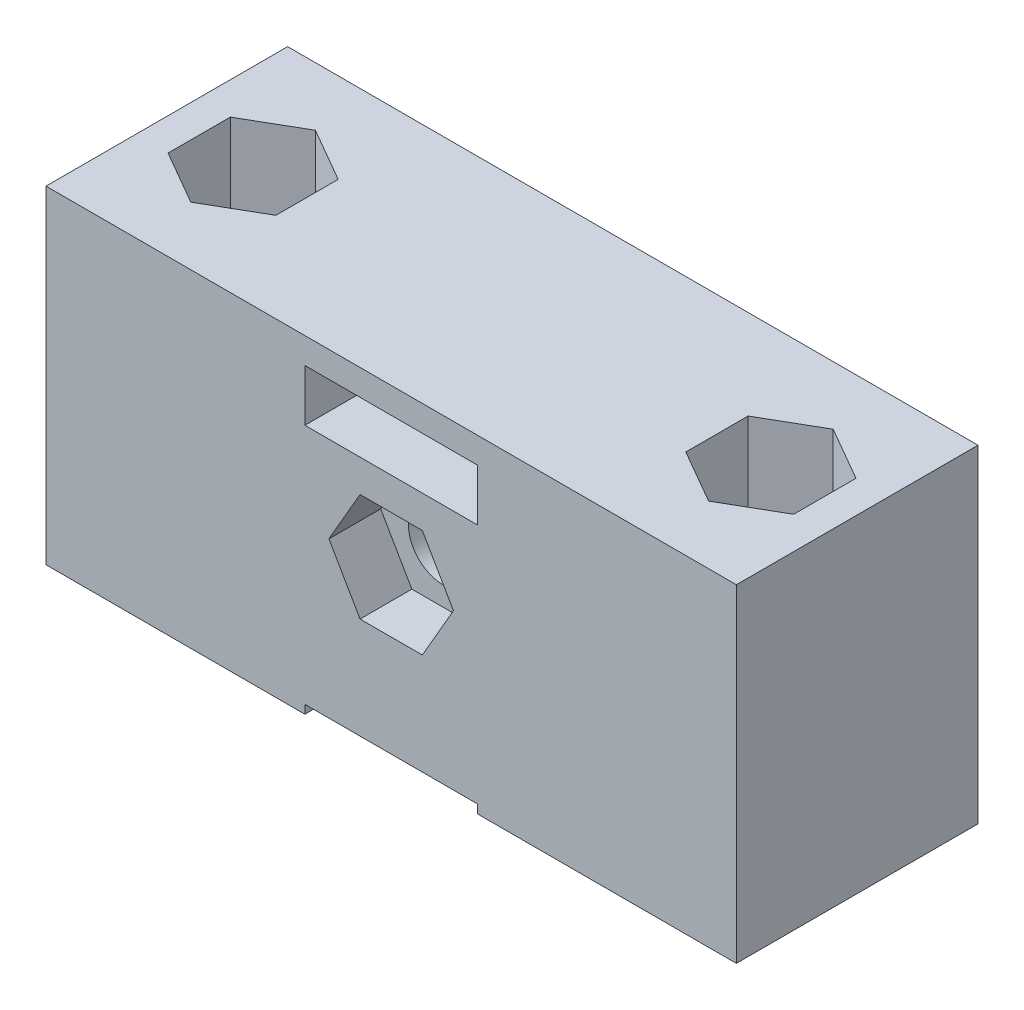
SolidWorks part; units mm, degrees
ref_plane "Front Plane" through (0, 0, 0) normal (0, 0, 1) x (1, 0, 0)
ref_plane "Top Plane" through (0, 0, 0) normal (0, 1, 0) x (1, 0, 0)
ref_plane "Right Plane" through (0, 0, 0) normal (1, 0, 0) x (0, 0, -1)
sketch "Sketch1" plane through (0, 0, 0) normal (0, 1, 0) x (1, 0, 0)
  line L1 (-20, 7) -> (20, 7)
  line L2 (-20, 7) -> (-20, -7)
  line L3 (-20, -7) -> (20, -7)
  line L4 (20, 7) -> (20, -7)
  line L5 (-20, 7) -> (20, -7) construction
  line L6 (-20, -7) -> (20, 7) construction
  point P0 (0, 0)
  dimension "D1" = 40
  dimension "D2" = 14
extrude "Boss-Extrude1" add sketch "Sketch1" along normal blind 19
sketch "Sketch2" plane through (0, 0, 7) normal (0, 0, 1) x (1, 0, 0)
  line L0 (0, 19) -> (0, 0) construction
  line L1 (-20, 19) -> (20, 19) construction
  line L3 (-5, 14.5) -> (5, 14.5)
  line L4 (-5, 14.5) -> (-5, 17.5)
  line L5 (-5, 17.5) -> (5, 17.5)
  line L6 (5, 14.5) -> (5, 17.5)
  line L7 (-5, 14.5) -> (5, 17.5) construction
  line L8 (-5, 17.5) -> (5, 14.5) construction
  line L9 (-5, -0.5) -> (5, -0.5)
  line L10 (-5, -0.5) -> (-5, 0.5)
  line L11 (-5, 0.5) -> (5, 0.5)
  line L12 (5, -0.5) -> (5, 0.5)
  line L13 (-5, -0.5) -> (5, 0.5) construction
  line L14 (-5, 0.5) -> (5, -0.5) construction
  point P5 (0, 16)
  dimension "D1" = 10
  dimension "D2" = 3
  dimension "D3" = 16
  dimension "D4" = 10
  dimension "D5" = 1
extrude "Cut-Extrude1" cut sketch "Sketch2" against normal blind 30
sketch "Sketch3" plane through (0, 0, 7) normal (0, 0, 1) x (1, 0, 0)
  line L0 (0, 19) -> (0, 0) construction
  line L1 (-20, 19) -> (20, 19) construction
  circle A0 centre (0, 9.5) radius 2
  dimension "D1" = 4
extrude "Cut-Extrude2" cut sketch "Sketch3" against normal through all
sketch "Sketch4" plane through (0, 19, 0) normal (0, 1, 0) x (1, 0, 0)
  line L0 (-20, 0) -> (20, 0) construction
  line L1 (-20, 7) -> (-20, -7) construction
  line L2 (20, -7) -> (20, 7) construction
  line L3 (0, 7) -> (0, -7) construction
  line L4 (20, 7) -> (-20, 7) construction
  line L5 (-20, -7) -> (20, -7) construction
  circle A0 centre (-15, 0) radius 1.6
  circle A1 centre (15, 0) radius 1.6
  dimension "D1" = 3.2
  dimension "D2" = 15
extrude "Cut-Extrude3" cut sketch "Sketch4" against normal through all
sketch "Sketch8" plane through (0, 0, 0) normal (0, -1, 0) x (-1, 0, 0)
  line L0 (-5, 7) -> (-5, -7) construction
  line L1 (5, -7) -> (-5, -7)
  line L2 (5, -7) -> (5, -6)
  line L3 (5, -6) -> (-5, -6)
  line L4 (-5, -7) -> (-5, -6)
  dimension "D1" = 1
extrude "Boss-Extrude2" [suppressed] add sketch "Sketch8" against normal up to next
sketch "Sketch9" plane through (0, 19, 0) normal (0, 1, 0) x (1, 0, 0)
  line L0 (0, 7) -> (0, -7) construction
  line L1 (-15, 3.6084) -> (-18.125, 1.8042)
  line L2 (-18.125, 1.8042) -> (-18.125, -1.8042)
  line L3 (-18.125, -1.8042) -> (-15, -3.6084)
  line L4 (-15, -3.6084) -> (-11.875, -1.8042)
  line L5 (-11.875, -1.8042) -> (-11.875, 1.8042)
  line L6 (-11.875, 1.8042) -> (-15, 3.6084)
  line L7 (20, 7) -> (-20, 7) construction
  line L8 (-20, -7) -> (20, -7) construction
  line L9 (11.875, 1.8042) -> (15, 3.6084)
  line L10 (11.875, -1.8042) -> (11.875, 1.8042)
  line L11 (15, -3.6084) -> (11.875, -1.8042)
  line L12 (18.125, -1.8042) -> (15, -3.6084)
  line L13 (18.125, 1.8042) -> (18.125, -1.8042)
  line L14 (15, 3.6084) -> (18.125, 1.8042)
  circle A0 centre (-15, 0) radius 3.125 construction
  circle A1 centre (15, 0) radius 3.125 construction
  dimension "D1" = 6.25
extrude "Cut-Extrude4" cut sketch "Sketch9" against normal blind 10
sketch "Sketch10" plane through (0, 0, 7) normal (0, 0, 1) x (1, 0, 0)
  line L1 (1.8042, 12.625) -> (-1.8042, 12.625)
  line L2 (-1.8042, 12.625) -> (-3.6084, 9.5)
  line L3 (-3.6084, 9.5) -> (-1.8042, 6.375)
  line L4 (-1.8042, 6.375) -> (1.8042, 6.375)
  line L5 (1.8042, 6.375) -> (3.6084, 9.5)
  line L6 (3.6084, 9.5) -> (1.8042, 12.625)
  circle A0 centre (0, 9.5) radius 3.125 construction
  dimension "D1" = 6.25
extrude "Cut-Extrude5" cut sketch "Sketch10" against normal blind 3
equation "\"X-ROD-SPACING\"=45"
equation "\"Y-ROD-SPACING\"=75"
equation "\"Z-ROD-SPACING\"=17.5"
equation "\"Y-BED-OFFSET\"=2"
equation "\"Y-BED-ROD-INSET\"=3.5"
equation "\"Y-BED-SCREW-SPACING\"=209"
equation "\"Y-BED-SCREW-CUTOUT-SLOT-HEIGHT\"=2.5"
equation "\"T-SLOT-NUT-FILLET-RADIUS\"=0.5"
equation "\"T-SLOT-SCREW-SHAFT-RADIUS\"=1.55"
equation "\"T-SLOT-SCREW-SHAFT-CUTOUT-LENGTH\"=11"
equation "\"T-SLOT-NUT-DEPTH\"=3.5"
equation "\"T-SLOT-NUT-WIDTH\"=2.85"
equation "\"T-SLOT-NUT-END-DISTANCE\"=8"
equation "\"ACRYLIC-THICKNESS\"=10"
equation "\"ACRYLIC-THICKNESS2\"=4.5"
equation "\"ACRYLIC-TAB-CUTOUT-SIZE\"=\"ACRYLIC-THICKNESS\"+\"ACRYLIC-TAB-TOLERANCE\"*2"
equation "\"ACRYLIC-TAB-TOLERANCE\"=-.05"
equation "\"ACRYLIC-TAB-WIDTH\"=\"ACRYLIC-THICKNESS\""
equation "\"ACRYLIC-M3-HOLE\"=2.9"
equation "\"SMOOTHROD-CAP-SCREW-DISTANCE\"=20"
equation "\"FRAME-WIDTH-INNER\"=370"
equation "\"NEMA17-HOLE-SPACING\"=31"
equation "\"NEMA17-CENTRAL-CUTOUT\"=22.5"
equation "\"Z-BRACKET-REACH\"=57"
equation "\"Z-ROD-INSET\"=13.5"
equation "\"TOP-BRACKET-SPACING\"=40"
equation "\"SMOOTHROD-X-LENGTH\"=350"
equation "\"SMOOTHROD-Y-LENGTH\"=350"
equation "\"SMOOTHROD-Z-LENGTH\"=350"
equation "\"SMOOTHROD-TIGHTENING-HEADROOM\"=.25"
equation "\"LEADSCREW-Z-LENGTH\"=300"
equation "\"SCREW-LENGTH-FRAME\"=\"ACRYLIC-THICKNESS\" + 10"
equation "\"SCREW-LENGTH-MOTOR\"=\"ACRYLIC-THICKNESS\" + 5"
equation "\"SCREW-LENGTH-EXTRUDER\"=28"
equation "\"SCREW-HEAD-RADIUS\"=6"
equation "\"PRINTED-M3-HOLE\"=3.5"
equation "\"PRINTED-X-SMOOTHROD-DIAMETER\"=8.8"
equation "\"PRINTED-X-SMOOTHROD-CUTOUT\"=10"
equation "\"PRINTED-X-BASE-HEIGHT\"=10"
equation "\"PRINTED-LM8UU-CUTOUT-SIZE\"=15.5"
equation "\"PRINTED-LM8UU-CUTOUT-LENGTH\"=24.5"
equation "\"PRINTED-X-IDLER-HEIGHT\"=16"
equation "\"PSU-MOUNTING-WIDTH\"=95"
equation "\"PSU-MOUNTING-HEIGHT\"=177"
equation "\"Y-BELT-TO-ROD-DISTANCE\"=20"
equation "\"SPOOL-HOLDER-ROD-SPACING\"=150"
equation "\"ACRYLIC-X-CARRIAGE-WIDTH\"=55"
equation "\"ACRYLIC-X-CARRIAGE-HEIGHT\"=75"
equation "\"ACRYLIC-X-CARRIAGE-LM8UU-CUTOUT-WIDTH\"=24.25"
equation "\"ACRYLIC-X-CARRIAGE-LM8UU-CUTOUT-HEIGHT\"=11.0"
equation "\"ACRYLIC-X-CARRIAGE-SCREW-SPACING-X\"=15"
equation "\"ACRYLIC-X-CARRIAGE-SCREW-SPACING-Y\"=33"
equation "\"ACRYLIC-X-CARRIAGE-CENTER-TAB-SPACING\"=14"
equation "\"ACRYLIC-X-CARRIAGE-EXTRUDER-OFFSET\"=26"
equation "\"ACRYLIC-X-CARRIAGE-EXTRUDER-ANGLE\"=90"
equation "\"ACRYLIC-X-CARRIAGE-EXTRUDER-SHELF-DEPTH\"=\"ACRYLIC-X-CARRIAGE-EXTRUDER-OFFSET\" + 28"
equation "\"ACRYLIC-X-CARRIAGE-EXTRUDER-BRACE-SPACING\"=23"
equation "\"ACRYLIC-X-CARRIAGE-EXTRUDER-BRACE-TAB-OFFSET\"=20"
equation "\"ACRYLIC-X-CARRIAGE-EXTRUDER-BRACE-HEIGHT\"=35"
equation "\"ACRYLIC-X-CARRIAGE-EXTRUDER-BRACE-SCREW-SPACING\"=22"
equation "\"ACRYLIC-X-CARRIAGE-DUAL-WIDTH-MULTIPLIER\"=1.65"
equation "\"ACRYLIC-X-CARRIAGE-DUAL-HOTEND-SPACING\"=42"
equation "\"ACRYLIC-X-CARRIAGE-DUAL-WIDTH\"=75"
equation "\"ACRYLIC-X-CARRIAGE-DUAL-HOTEND-SEPARATION\"=36"
equation "\"ACRYLIC-X-CARRIAGE-DUAL-MOUNT-PLATE-DEPTH\"=75"
equation "\"ACRYLIC-X-CARRIAGE-DUAL-MOUNT-BRACE-WIDTH\"=33"
equation "\"ACRYLIC-X-CARRIAGE-DUAL-MOUNT-SCREW-WIDTH\"=40"
equation "\"BLOWER-FAN-WIDTH\"=15"
equation "\"PRINTED-M3-NUT-AF\"=6.25"
equation "\"D1@Sketch9\"=\"PRINTED-M3-NUT-AF\""
equation "\"D1@Sketch10\"=\"PRINTED-M3-NUT-AF\""
